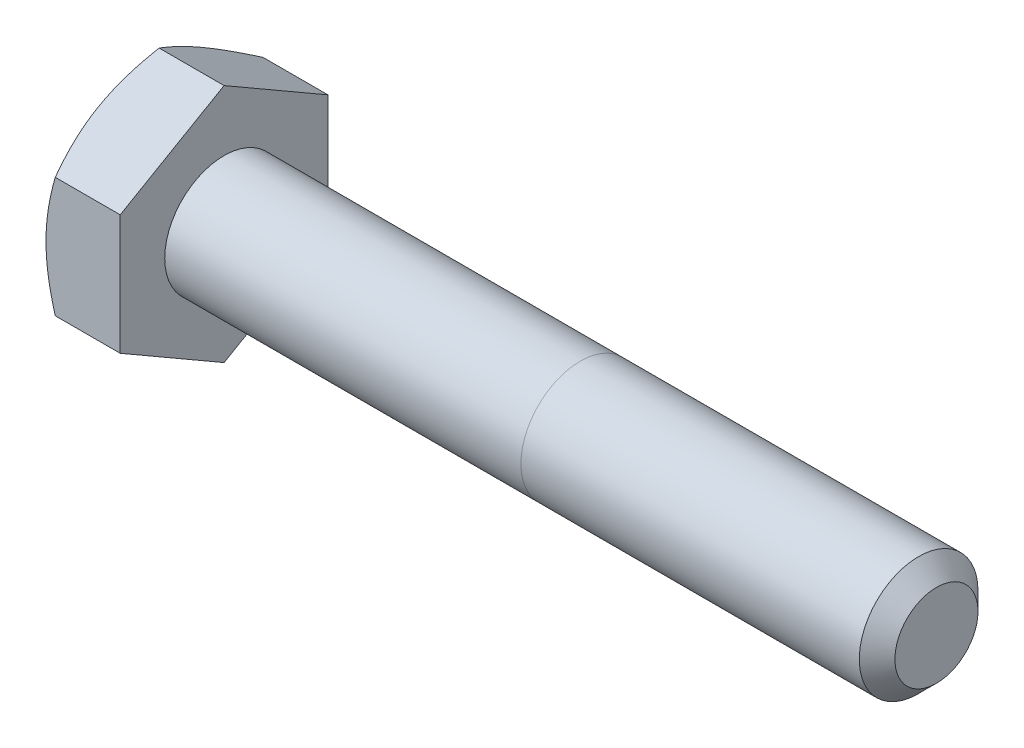
SolidWorks part; units mm, degrees
material "Alloy Steel"
ref_plane "Front Plane" through (0, 0, 0) normal (0, 0, 1) x (1, 0, 0)
ref_plane "Top Plane" through (0, 0, 0) normal (0, 1, 0) x (1, 0, 0)
ref_plane "Right Plane" through (0, 0, 0) normal (1, 0, 0) x (0, 0, -1)
sketch "Sketch1" plane through (0, 0, 0) normal (0, 0, 1) x (1, 0, 0)
  line L0 (-21.0344, 0) -> (21.0344, 0) construction
  line L1 (21.0344, 3.175) -> (21.0344, -3.175) construction
  line L2 (-17.0656, 5.5562) -> (-17.0656, -5.5562) construction
  line L3 (-21.0344, 5.5562) -> (-21.0344, -5.5562) construction
  point P9 (-17.0656, 0)
  point P10 (16.5894, -3.175)
  dimension "D1" = 4.445
  dimension "Screw Dia" = 6.35
  dimension "Hex" = 11.1125
  dimension "Head Ht" = 3.9688
  dimension "Screw Lenght" = 38.1
ref_plane "Plane2" through (21.0344, 0, 0) normal (1, 0, 0) x (0, 0, -1)
sketch "Sketch5" plane through (21.0344, 0, 0) normal (1, 0, 0) x (0, 0, -1)
  circle A0 centre (0, 0) radius 3.175
extrude "Boss-Extrude3" add sketch "Sketch5" against normal up to vertex (38.1 mm away) up to point (-17.0656, 0, 0)
sketch "Sketch9" plane through (21.0344, 0, 0) normal (1, 0, 0) x (0, 0, -1)
  circle A1 centre (0, 0) radius 3.175
  circle A2 centre (0, 0) radius 3.175
  dimension "D1" = 0
curve "Helix/Spiral1" [suppressed] pitch 1.27 height 20.32 turns 16 parameters "Pitch"=1.27
chamfer "Chamfer1" distance 0.9525 angle 45 1 edges at (21.0344, 0, -3.175)
sketch "Sketch10" plane through (0, 0, 0) normal (0, 0, 1) x (1, 0, 0)
  line L0 (21.0344, 3.175) -> (21.5106, 2.3501)
  line L1 (21.5106, 2.3501) -> (21.6694, 2.3501)
  line L2 (21.6694, 2.3501) -> (22.1456, 3.175)
  line L3 (21.0344, 3.175) -> (22.1456, 3.175)
  line L4 (21.59, 3.175) -> (21.59, 2.3501) construction
  line L5 (21.2725, 2.7626) -> (21.9075, 2.7626) construction
  dimension "D1" = 60
  dimension "D2" = 0.1588
  dimension "D3" = 0.635
sweep "Cut-Sweep1" [suppressed] cut profiles "Sketch10" path "Helix/Spiral1"
sketch "Sketch11" plane through (0, 0, 0) normal (0, 0, 1) x (1, 0, 0)
  line L0 (-17.0656, 3.175) -> (-17.0656, 0)
  line L1 (-17.0656, 0) -> (5.1594, 0)
  line L3 (5.1594, 0) -> (1.9844, 3.175)
  line L4 (-17.0656, 3.175) -> (1.9844, 3.175)
  dimension "D1" = 45
  dimension "MIn Thread" = 19.05
revolve "Revolve1" add sketch "Sketch11" angle 360 about L1
sketch "Sketch6" plane through (-17.0656, 0, 0) normal (-1, 0, 0) x (0, 0, 1)
  line L0 (0, 5.5562) -> (0, -5.5562) construction
  line L1 (5.5563, 3.2079) -> (0, 6.4158)
  line L2 (0, 6.4158) -> (-5.5562, 3.2079)
  line L3 (-5.5562, 3.2079) -> (-5.5562, -3.2079)
  line L4 (-5.5562, -3.2079) -> (0, -6.4158)
  line L5 (0, -6.4158) -> (5.5563, -3.2079)
  line L6 (5.5563, -3.2079) -> (5.5563, 3.2079)
  circle A0 centre (0, 0) radius 5.5563 construction
extrude "Boss-Extrude4" add sketch "Sketch6" along normal up to vertex (3.9688 mm away) up to point (-21.0344, -5.5562, 0)
sketch "Sketch7" plane through (-21.0344, 0, 0) normal (-1, 0, 0) x (0, 0, 1)
  circle A0 centre (0, 0) radius 5.5563 construction
  circle A1 centre (0, 0) radius 5.5563
sketch "Sketch8" plane through (-21.0344, 0, 0) normal (-1, 0, 0) x (0, 0, 1)
  circle A0 centre (0, 0) radius 5.5563 construction
  circle A1 centre (0, 0) radius 5.5563
extrude "Cut-Extrude3" cut sketch "Sketch8" against normal through all draft 60 flip side to cut
sketch "Sketch12" plane through (-21.0344, 0, 0) normal (-1, 0, 0) x (0, 0, 1)
  line L0 (0, 4.2783) -> (0, 2.3892) construction
  line L1 (0.1667, 4.2783) -> (0.1667, 2.3892)
  line L2 (-0.1667, 4.2783) -> (-0.1667, 2.3892)
  line L3 (0, 3.175) -> (0, -3.175) construction
  arc A0 (0.1667, 4.2783) -> (-0.1667, 4.2783) centre (0, 4.2783) ccw
  arc A1 (-0.1667, 2.3892) -> (0.1667, 2.3892) centre (0, 2.3892) ccw
  circle A3 centre (0, 0) radius 2.2225 construction
  circle A4 centre (0, 0) radius 4.445 construction
  point P2 (0, 3.3337)
  dimension "D1" = 4.445
  dimension "D3" = 8.89
  dimension "D2" = 0.3334
extrude "Cut-Extrude4" cut sketch "Sketch12" against normal blind 0.254
pattern_circular "CirPattern1" count 3 over 360 about axis through (-17.0656, 0, 0) along (1, 0, 0) of "Cut-Extrude4"
sketch "Sketch13" plane through (0, 0, 0) normal (0, 1, 0) x (1, 0, 0)
  line L0 (1.9844, 3.175) -> (1.9844, -3.175)
  line L1 (20.0819, 3.175) -> (-17.0656, 3.175) construction
  line L2 (-17.0656, -3.175) -> (20.0819, -3.175) construction
  line L4 (21.0344, -2.2225) -> (21.0344, 2.2225) construction
  point P8 (1.9844, 0)
  dimension "D1" = 19.05
split line "Split Line1"
equation "\"D2@Sketch10\" = \"Pitch@Helix/Spiral1\"*.125"
equation "\"D3@Sketch10\" = \"Pitch@Helix/Spiral1\"*.5"
equation "\"D3@Helix/Spiral1\" = \"MIn Thread@Sketch11\"+\"Pitch@Helix/Spiral1\""
equation "\"D1@Chamfer1\" = \"Pitch@Helix/Spiral1\"*.75"
equation "\"D1@Sketch12\" = \"Hex@Sketch1\"*.4"
equation "\"D3@Sketch12\" = \"Hex@Sketch1\"*.8"
equation "\"D2@Sketch12\" = \"Hex@Sketch1\"*.03"
equation "\"D1@Sketch1\" = \"Pitch@Helix/Spiral1\"*3.5"
